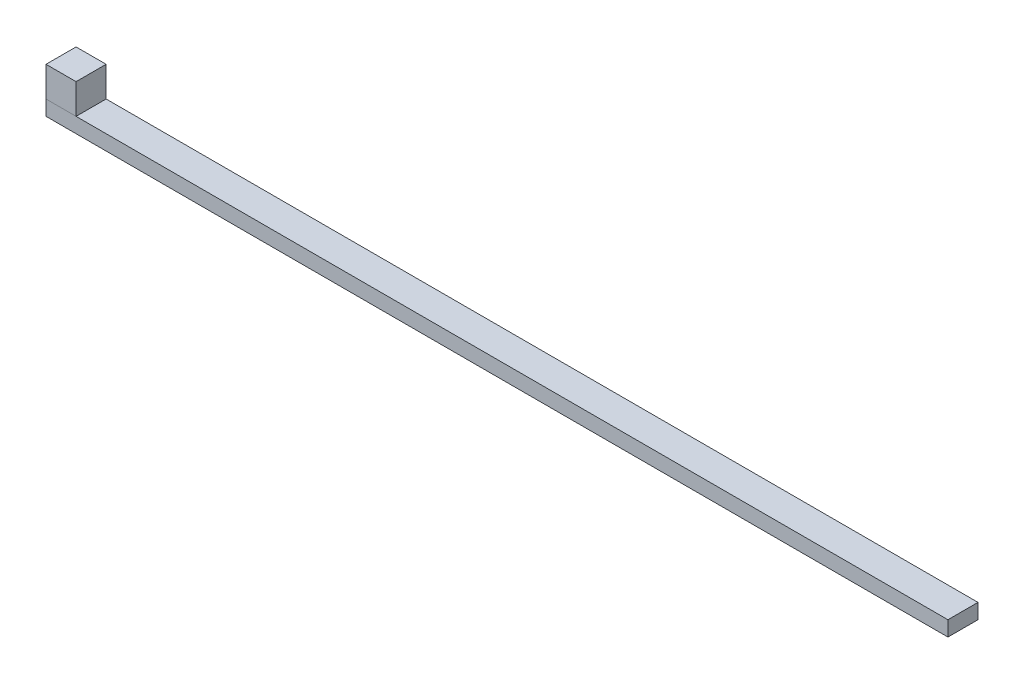
SolidWorks part; units mm, degrees
ref_plane "正面" through (0, 0, 0) normal (0, 0, 1) x (1, 0, 0)
ref_plane "平面" through (0, 0, 0) normal (0, 1, 0) x (1, 0, 0)
ref_plane "右側面" through (0, 0, 0) normal (1, 0, 0) x (0, 0, -1)
sketch "ｽｹｯﾁ1" plane through (0, 0, 0) normal (0, 0, 1) x (1, 0, 0)
  line L1 (0, 0) -> (3000, 0)
  line L2 (0, 0) -> (0, -50)
  line L3 (0, -50) -> (3000, -50)
  line L4 (3000, 0) -> (3000, -50)
  line L5 (0, 0) -> (100, 0)
  line L6 (0, 0) -> (0, 100)
  line L7 (0, 100) -> (100, 100)
  line L8 (100, 0) -> (100, 100)
extrude "ﾎﾞｽ - 押し出し1" add sketch "ｽｹｯﾁ1" along normal blind 100 contours L4 L1 L2 L3 region at (1500, -25, 0)
extrude "ﾎﾞｽ - 押し出し2" add sketch "ｽｹｯﾁ1<3>" along normal blind 100 separate body contours L1 L8 L7 L6 region at (50, 50, 0)
sketch "ｽｹｯﾁ1<3>" plane through (0, 0, 0) normal (0, 0, 1) x (1, 0, 0) same geometry as "ｽｹｯﾁ1"
